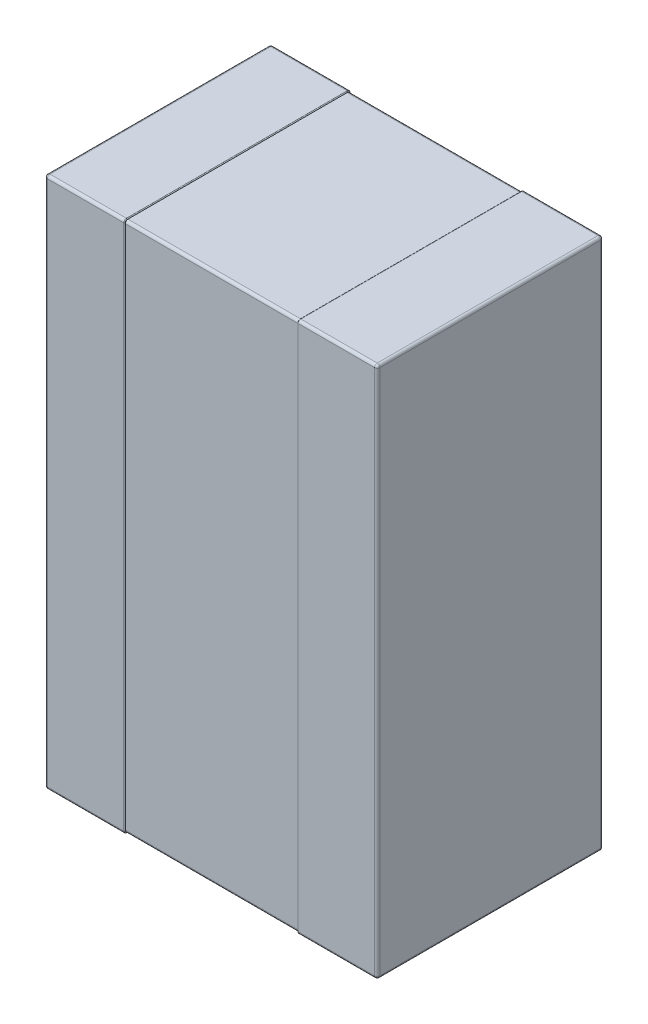
SolidWorks part; units mm, degrees
ref_plane "Top Plane" through (0, 0, 0) normal (0, 0, 1) x (1, 0, 0)
ref_plane "Front Plane" through (0, 0, 0) normal (0, 1, 0) x (1, 0, 0)
ref_plane "Side Plane" through (0, 0, 0) normal (1, 0, 0) x (0, 0, -1)
sketch "Sketch1" plane through (0, 0, 0) normal (0, 0, 1) x (1, 0, 0)
  line L1 (-0.625, 1) -> (0.625, 1)
  line L2 (-0.625, 1) -> (-0.625, -1)
  line L3 (-0.625, -1) -> (0.625, -1)
  line L4 (0.625, 1) -> (0.625, -1)
  dimension "D1" = 1.25
  dimension "D2" = 0.625
  dimension "D3" = 2
  dimension "D4" = 1
extrude "All body" add sketch "Sketch1" along normal blind 0.85
sketch "Sketch2" plane through (0, 0, 0) normal (1, 0, 0) x (0, 0, -1)
  line L14 (-0.003, 0.997) -> (-0.847, 0.997)
  line L15 (-0.003, -0.997) -> (-0.003, 0.997)
  line L16 (-0.847, -0.997) -> (-0.003, -0.997)
  line L17 (-0.847, 0.997) -> (-0.847, -0.997)
  line L18 (-0.003, 0.997) -> (-0.847, 0.997)
  line L19 (-0.003, -0.997) -> (-0.003, 0.997)
  line L20 (-0.847, -0.997) -> (-0.003, -0.997)
  line L21 (-0.847, 0.997) -> (-0.847, -0.997)
  dimension "D1" = 0.003
extrude "Cut out the body for pin" cut sketch "Sketch2" against normal blind 0.325 and the other way blind 0.325 flip side to cut
fillet "Body fillet" radius 0.01 4 edges at (0, 0.997, 0.003) (0, 0.997, 0.847) (0, -0.997, 0.003) (0, -0.997, 0.847)
fillet "Pin fillet a" radius 0.01 16 edges at (0.625, -1, 0.425) (0.625, 0, 0.85) (0.625, 1, 0.425) (0.625, 0, 0) (-0.625, 1, 0.425) (-0.625, 0, 0.85) (-0.625, -1, 0.425) (-0.625, 0, 0) (0.475, 1, 0.85) (0.475, -1, 0.85) (0.475, -1, 0) (0.475, 1, 0) (-0.475, 1, 0) (-0.475, -1, 0) (-0.475, 1, 0.85) (-0.475, -1, 0.85)
fillet "Pin fillet b" radius 0.003 16 edges at (0.325, -0.9971, 0.8471) (0.325, -1, 0.425) (0.325, -0.9971, 0.0029) (0.325, 0, 0) (0.325, 0.9971, 0.0029) (0.325, 1, 0.425) (0.325, 0.9971, 0.8471) (-0.325, -0.9971, 0.8471) (-0.325, -1, 0.425) (-0.325, -0.9971, 0.0029) (-0.325, 0, 0) (-0.325, 0.9971, 0.0029) (-0.325, 1, 0.425) (-0.325, 0.9971, 0.8471) (0.325, 0, 0.85) (-0.325, 0, 0.85)
